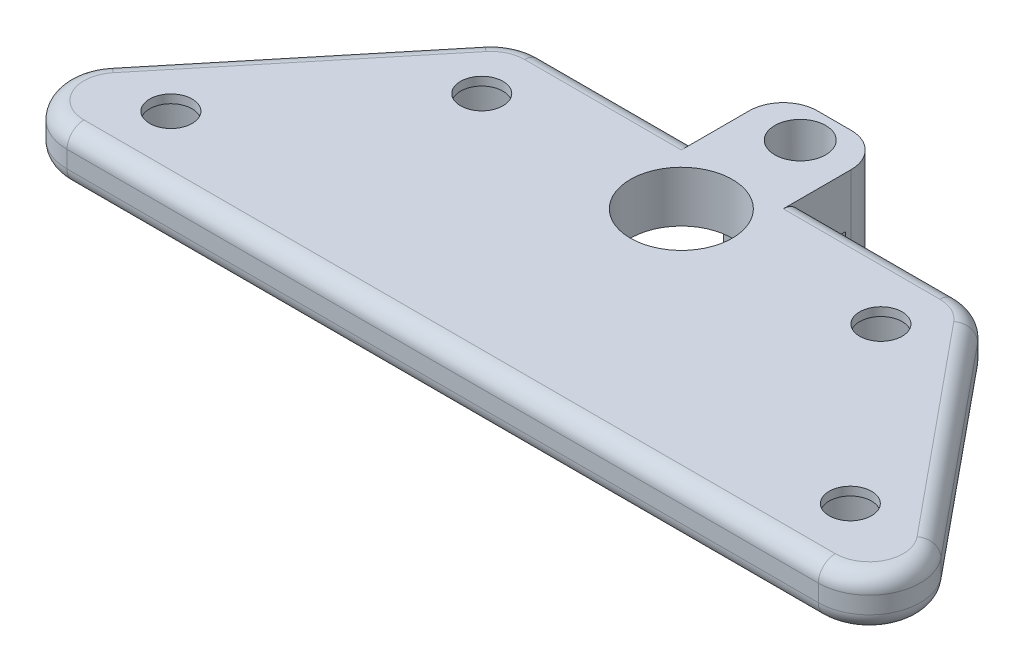
SolidWorks part; units mm, degrees
ref_plane "Front Plane" through (0, 0, 0) normal (0, 0, 1) x (1, 0, 0)
ref_plane "Top Plane" through (0, 0, 0) normal (0, 1, 0) x (1, 0, 0)
ref_plane "Right Plane" through (0, 0, 0) normal (1, 0, 0) x (0, 0, -1)
sketch "Sketch1" plane through (0, 0, 0) normal (0, 1, 0) x (1, 0, 0)
  line L0 (-11.75, 0) -> (11.75, 0) construction
  line L1 (0, 0) -> (0, -10.05) construction
  line L2 (-20, -10.05) -> (20, -10.05) construction
  line L3 (11.75, 0) -> (20, -10.05) construction
  line L4 (-11.75, 0) -> (-20, -10.05) construction
  line L5 (-14.5417, 2.9035) -> (-24.4335, -9.1465)
  line L6 (-22.1147, -14.05) -> (22.1147, -14.05)
  line L7 (14.5417, 2.9035) -> (24.4335, -9.1465)
  line L8 (-12.2229, 4) -> (-3, 4)
  line L9 (-13.6415, 4) -> (-28.4587, -14.05) construction
  line L10 (-13.6415, 4) -> (13.6415, 4) construction
  line L11 (13.6415, 4) -> (28.4587, -14.05) construction
  line L12 (-28.4587, -14.05) -> (28.4587, -14.05) construction
  line L13 (0, 9) -> (0, 0) construction
  line L14 (-1, 9) -> (1, 9)
  line L15 (3, 7) -> (3, 4)
  line L16 (3, 4) -> (12.2229, 4)
  line L17 (-3, 7) -> (-3, 4)
  circle A0 centre (0, 0) radius 3
  circle A1 centre (11.75, 0) radius 2.6
  circle A2 centre (20, -10.05) radius 2.6
  circle A3 centre (-20, -10.05) radius 2.6
  circle A4 centre (-11.75, 0) radius 2.6
  arc A5 (-14.5417, 2.9035) -> (-12.2229, 4) centre (-12.2229, 1) cw
  arc A6 (14.5417, 2.9035) -> (12.2229, 4) centre (12.2229, 1) ccw
  arc A7 (22.1147, -14.05) -> (24.4335, -9.1465) centre (22.1147, -11.05) ccw
  arc A8 (-24.4335, -9.1465) -> (-22.1147, -14.05) centre (-22.1147, -11.05) ccw
  circle A9 centre (0, 7) radius 1.5
  arc A10 (1, 9) -> (3, 7) centre (1, 7) cw
  arc A11 (-3, 7) -> (-1, 9) centre (-1, 7) cw
  point P37 (3, 9)
  point P40 (-3, 9)
  dimension "D3" = 6
  dimension "D4" = 4
  dimension "D6" = 5.2
  dimension "D7" = 3
  dimension "D10" = 2
  dimension "D12" = 3
  dimension "D1" = 11.75
  dimension "D2" = 10.05
  dimension "D5" = 20
  dimension "D8" = 3
  dimension "D9" = 5
  dimension "D11" = 2
extrude "Boss-Extrude1" add sketch "Sketch1" along normal blind 3
sketch "Sketch3" plane through (0, 3, 0) normal (0, 1, 0) x (1, 0, 0)
  circle A0 centre (-11.75, 0) radius 2.6
  circle A1 centre (-20, -10.05) radius 2.6
  circle A2 centre (11.75, 0) radius 2.6
  circle A3 centre (20, -10.05) radius 2.6
  circle A4 centre (-20, -10.05) radius 1.25
  circle A5 centre (-11.75, 0) radius 1.25
  circle A6 centre (11.75, 0) radius 1.25
  circle A7 centre (20, -10.05) radius 1.25
  dimension "D1" = 5.2
  dimension "D2" = 2.5
extrude "Boss-Extrude3" add sketch "Sketch3" against normal blind 0.5
sketch "Sketch4" plane through (0, 0, 0) normal (0, -1, 0) x (-1, 0, 0)
  line L0 (-3, 4) -> (-3, 7)
  line L1 (-3, 4) -> (-3, 7) construction
  line L3 (3, 7) -> (3, 4)
  line L4 (3, 7) -> (3, 4) construction
  line L5 (3, 4) -> (-3, 4)
  line L6 (-1, 9) -> (1, 9)
  arc A0 (-1, 9) -> (-3, 7) centre (-1, 7) ccw
  arc A2 (3, 7) -> (1, 9) centre (1, 7) ccw
  circle A3 centre (0, 7) radius 1.5
  dimension "D1" = 3
extrude "Boss-Extrude4" add sketch "Sketch4" along normal blind 3.4
fillet "Fillet1" radius 1 18 edges at (-7.6114, 0, -4) (-13.5054, 0, -3.7121) (7.6114, 0, -4) (13.5054, 0, -3.7121) (19.4876, 0, 3.1215) (24.8267, 0, 12.3325) (0, 0, 14.05) (-24.8267, 0, 12.3325) (-7.6114, 3, -4) (-13.5054, 3, -3.7121) (7.6114, 3, -4) (13.5054, 3, -3.7121) (19.4876, 3, 3.1215) (24.8267, 3, 12.3325) (0, 3, 14.05) (-24.8267, 3, 12.3325) (-19.4876, 0, 3.1215) (-19.4876, 3, 3.1215)
sketch "Sketch5" plane through (0, -3.4, 0) normal (0, -1, 0) x (-1, 0, 0)
  circle A0 centre (-11.75, 0) radius 11
  circle A1 centre (11.75, 0) radius 11
  dimension "D1" = 22
extrude "Cut-Extrude1" cut sketch "Sketch5" against normal blind 3.4
